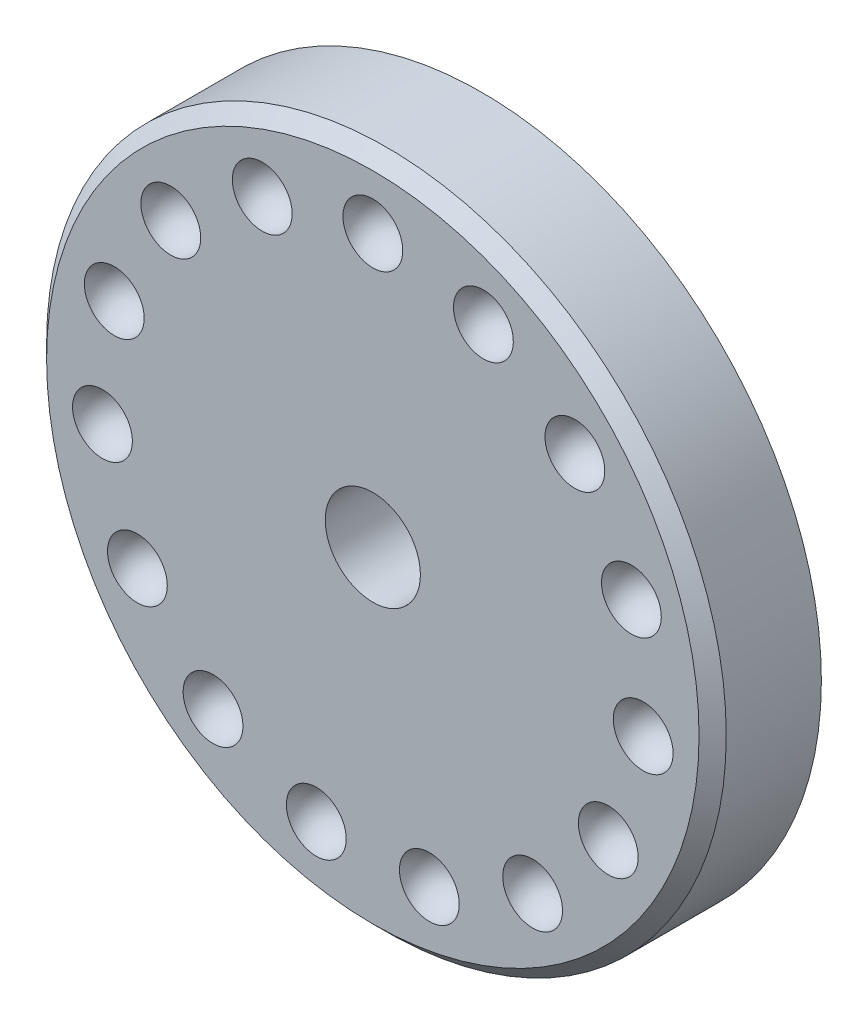
SolidWorks part; units mm, degrees
ref_plane "Front Plane" through (0, 0, 0) normal (0, 0, 1) x (1, 0, 0)
ref_plane "Top Plane" through (0, 0, 0) normal (0, 1, 0) x (1, 0, 0)
ref_plane "Right Plane" through (0, 0, 0) normal (1, 0, 0) x (0, 0, -1)
sketch "Sketch1" plane through (0, 0, 0) normal (0, 0, 1) x (1, 0, 0)
  circle A0 centre (0, 0) radius 12.5
  dimension "D1" = 25
extrude "Boss-Extrude1" add sketch "Sketch1" along normal blind 4
ref_axis "Axis1" through (0, 0, -0.35) along (0, 0, 1)
chamfer "Chamfer1" distance 0.5 angle 45 1 edges at (12.5, 0, 4)
ref_axis "Axis2" through (0, 14.0125, 4) along (0, -1, 0)
sketch "Sketch6" plane through (0, 0, 0) normal (1, 0, 0) x (0, 0, -1)
  line L0 (-4, 14.0125) -> (-4, -13.7625) construction
  line L1 (-4, 8.9) -> (-4, 11.1)
  line L2 (0, 12.5) -> (-3.5, 12.5) construction
  arc A0 (-4, 11.1) -> (-4, 8.9) centre (-4, 10) ccw
  dimension "D1" = 2.2
  dimension "D2" = 2.5
revolve "Cut-Revolve2" cut sketch "Sketch6" angle 360 about L1
pattern_circular "CirPattern1" count 15 over 360 about axis through (0, 0, 3.5) along (0, 0, -1) of "Cut-Revolve2"
sketch "Sketch7" plane through (0, 0, 4) normal (0, 0, 1) x (1, 0, 0)
  circle A0 centre (0, 0) radius 1.25
  dimension "D1" = 2.5
extrude "Cut-Extrude1" cut sketch "Sketch7" against normal through all
sketch "Sketch10" plane through (0, 0, 4) normal (0, 0, 1) x (1, 0, 0)
  circle A0 centre (0, 0) radius 1.75
  dimension "D1" = 3.5
extrude "Cut-Extrude2" cut sketch "Sketch10" against normal through all
